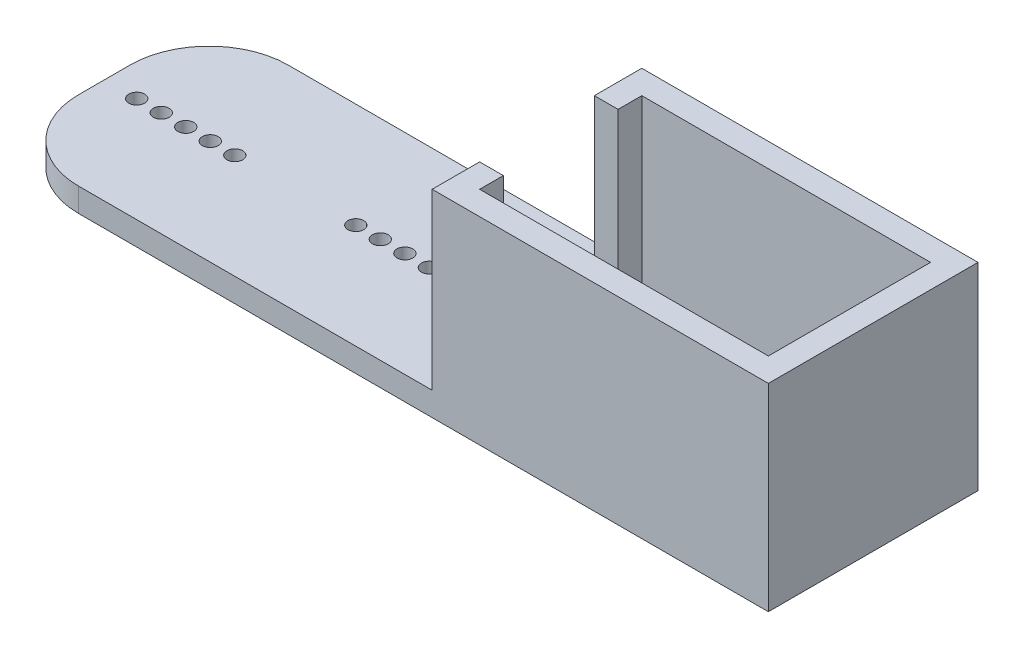
SolidWorks part; units mm, degrees
ref_plane "Front Plane" through (0, 0, 0) normal (0, 0, 1) x (1, 0, 0)
ref_plane "Top Plane" through (0, 0, 0) normal (0, 1, 0) x (1, 0, 0)
ref_plane "Right Plane" through (0, 0, 0) normal (1, 0, 0) x (0, 0, -1)
sketch "Sketch1" plane through (0, 0, 0) normal (0, 1, 0) x (1, 0, 0)
  line L1 (-48.6, -13.25) -> (48.6, -13.25)
  line L2 (-48.6, -13.25) -> (-48.6, 13.25)
  line L3 (-48.6, 13.25) -> (48.6, 13.25)
  line L4 (48.6, -13.25) -> (48.6, 13.25)
  line L5 (-48.6, -13.25) -> (48.6, 13.25) construction
  line L6 (-48.6, 13.25) -> (48.6, -13.25) construction
  point P0 (0, 0)
  dimension "D1" = 26.5
  dimension "D2" = 97.2
extrude "Boss-Extrude1" add sketch "Sketch1" along normal blind 3
sketch "Sketch2" plane through (0, 3, 0) normal (0, 1, 0) x (1, 0, 0)
  line L0 (48.6, 13.25) -> (-48.6, 13.25) construction
  line L1 (48.6, -13.25) -> (9.1, -13.25)
  line L2 (48.6, -13.25) -> (48.6, 13.25)
  line L3 (48.6, 13.25) -> (45.6, 13.25)
  line L5 (45.6, 13.25) -> (9.6, 13.25)
  line L6 (45.6, 10.25) -> (9.1, 10.25)
  line L12 (45.6, -10.25) -> (9.1, -10.25)
  line L15 (45.6, -10.25) -> (45.6, 10.25)
  line L16 (9.1, 10.25) -> (9.1, 7.25)
  line L17 (9.1, 7.25) -> (6.1, 7.25)
  line L18 (6.1, 7.25) -> (6.1, 13.25)
  line L19 (9.1, -10.25) -> (9.1, -7.25)
  line L20 (9.1, -7.25) -> (6.1, -7.25)
  line L21 (6.1, -7.25) -> (6.1, -13.25)
  line L22 (-48.6, -13.25) -> (48.6, -13.25) construction
  line L23 (6.1, 13.25) -> (9.6, 13.25)
  line L24 (9.1, -13.25) -> (6.1, -13.25)
  dimension "D1" = 3
  dimension "D2" = 36.5
  dimension "D3" = 3
  dimension "D4" = 3
  dimension "D5" = 3
  dimension "D6" = 3
  dimension "D7" = 3
extrude "Boss-Extrude2" add sketch "Sketch2" along normal blind 22
sketch "Sketch3" plane through (0, 3, 0) normal (0, 1, 0) x (1, 0, 0)
  line L0 (9.1, 10.25) -> (45.6, 10.25) construction
  line L1 (19.1, 10.25) -> (23.6, 10.25)
  line L2 (19.1, 10.25) -> (19.1, -10.25)
  line L3 (19.1, -10.25) -> (23.6, -10.25)
  line L4 (23.6, 10.25) -> (23.6, -10.25)
  line L5 (45.6, -10.25) -> (9.1, -10.25) construction
  line L6 (9.1, -10.25) -> (9.1, -7.25) construction
  dimension "D1" = 4.5
  dimension "D2" = 10
extrude "Cut-Extrude1" cut sketch "Sketch3" against normal through all
sketch "Sketch4" plane through (0, 3, 0) normal (0, 1, 0) x (1, 0, 0)
  line L0 (-24.45, 13.25) -> (-24.45, -13.25)
  line L1 (6.1, 13.25) -> (-48.6, 13.25) construction
  line L2 (-48.6, -13.25) -> (6.1, -13.25) construction
  line L3 (45.6, 10.25) -> (45.6, -10.25) construction
  dimension "D1" = 70.05
sketch "Sketch5" plane through (0, 3, 0) normal (0, 1, 0) x (1, 0, 0)
  line L0 (-48.6, 0) -> (45.6, 0) construction
  line L1 (-48.6, 13.25) -> (-48.6, -13.25) construction
  line L2 (45.6, 10.25) -> (45.6, -10.25) construction
  line L3 (-16.8, 0) -> (-24.45, 0) construction
  line L5 (-24.45, 13.25) -> (-24.45, -13.25) construction
  line L6 (-24.45, 13.25) -> (-24.45, -13.25) construction
  line L7 (-24.45, 0) -> (-32.1, 0) construction
  circle A0 centre (-32.1, 0) radius 1
  circle A1 centre (-16.8, 0) radius 1
  circle A2 centre (-13.7, 0) radius 1
  circle A3 centre (-10.6, 0) radius 1
  circle A4 centre (-7.5, 0) radius 1
  circle A5 centre (-4.4, 0) radius 1
  circle A6 centre (-35.2, 0) radius 1
  circle A7 centre (-38.3, 0) radius 1
  circle A8 centre (-41.4, 0) radius 1
  circle A9 centre (-44.5, 0) radius 1
  dimension "D1" = 5
  dimension "D2" = 2
  dimension "D4" = 15.3
  dimension "D3" = 5
extrude "Cut-Extrude2" cut sketch "Sketch5" against normal through all
fillet "Fillet1" radius 10 2 edges at (-48.6, 1.5, -13.25) (-48.6, 1.5, 13.25)
